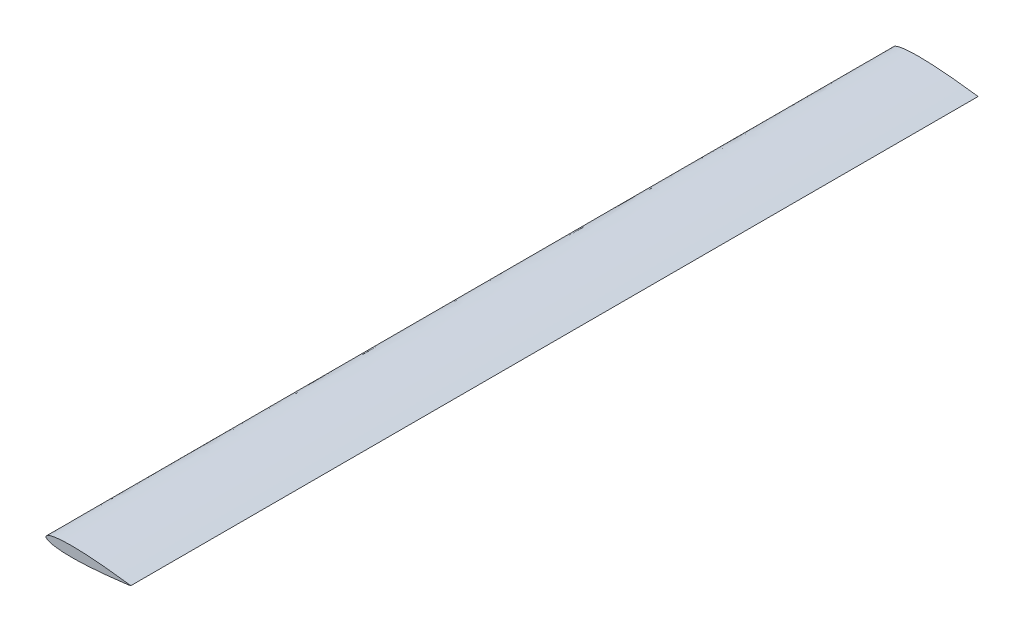
SolidWorks part; units mm, degrees
material "Custom Polymer"
ref_plane "Front Plane" through (0, 0, 0) normal (0, 0, 1) x (1, 0, 0)
ref_plane "Top Plane" through (0, 0, 0) normal (0, 1, 0) x (1, 0, 0)
ref_plane "Right Plane" through (0, 0, 0) normal (1, 0, 0) x (0, 0, -1)
sketch "Sketch1" plane through (0, 0, 0) normal (0, 0, 1) x (1, 0, 0)
  line L0 (0, 0) -> (1000, 0) construction
  spline S4 degree 3 poles (0.4143, 4.3853) (-0.2008, 0.0001) (0.4094, -4.3857) (2.2543, -8.6603) (5.2707, -12.775) (9.422, -16.7475) (14.6946, -20.592) (21.081, -24.312) (28.5717, -27.9033) (37.1535, -31.3578) (46.8093, -34.6651) (57.5186, -37.8143) (69.2578, -40.7934) (82.0003, -43.5917) (95.717, -46.1976) (110.3762, -48.6018) (125.9441, -50.7943) (142.3846, -52.7677) (159.6593, -54.5151) (177.7281, -56.0316) (196.5487, -57.3135) (216.0775, -58.3589) (236.2687, -59.1679) (257.0752, -59.7419) (278.4485, -60.0841) (300.3387, -60.1994) (322.6946, -60.0941) (345.4641, -59.7758) (368.5941, -59.2535) (392.0304, -58.5372) (415.7184, -57.6376) (439.6028, -56.5665) (463.6278, -55.336) (487.7372, -53.9588) (511.8749, -52.4476) (535.9844, -50.8155) (560.0094, -49.0752) (583.8939, -47.2399) (607.5819, -45.322) (631.0183, -43.3341) (654.1483, -41.2882) (676.9179, -39.1961) (699.2738, -37.0696) (721.1639, -34.9196) (742.5371, -32.7573) (763.3433, -30.5932) (783.5341, -28.438) (803.0622, -26.3022) (821.8821, -24.1954) (839.9497, -22.1283) (857.223, -20.1106) (873.6615, -18.1522) (889.2267, -16.2628) (903.8825, -14.4523) (917.5946, -12.7298) (930.3308, -11.1051) (942.0615, -9.5864) (952.7594, -8.1834) (962.3991, -6.9024) (970.9591, -5.7556) (978.4165, -4.737) (984.7625, -3.8911) (989.9579, -3.1155) (994.0559, -2.7031) (996.8878, -1.9572) (999.5116, -2.4521) (1000.4888, 0.7707) (998.6373, 0.7843) (996.9769, 1.1296) (994.0179, 1.481) (989.9767, 2.0732) (984.7604, 2.7864) (978.4232, 3.6639) (970.9642, 4.6823) (962.4063, 5.8413) (952.7678, 7.1321) (942.0716, 8.5471) (930.3425, 10.0787) (917.6081, 11.7175) (903.8979, 13.4551) (889.2441, 15.2818) (873.6809, 17.1884) (857.2446, 19.1649) (839.9736, 21.2016) (821.9083, 23.2886) (803.0908, 25.4162) (783.565, 27.5735) (763.3766, 29.751) (742.5728, 31.9381) (721.202, 34.124) (699.3143, 36.2981) (676.9607, 38.4492) (654.1935, 40.5664) (631.0658, 42.6379) (607.6316, 44.6517) (583.9456, 46.5957) (560.0632, 48.4573) (536.0401, 50.2241) (511.9324, 51.8829) (487.7965, 53.4207) (463.6885, 54.8245) (439.6649, 56.0815) (415.7818, 57.179) (392.0947, 58.1047) (368.6592, 58.8468) (345.5299, 59.3946) (322.7607, 59.7381) (300.4049, 59.868) (278.5146, 59.7768) (257.1409, 59.4583) (236.3338, 58.9072) (216.1417, 58.1205) (196.6118, 57.0967) (177.7898, 55.8354) (159.7194, 54.3389) (142.4427, 52.6106) (126.0001, 50.6553) (110.4297, 48.48) (95.7679, 46.092) (82.0483, 43.5012) (69.3028, 40.717) (57.5603, 37.7508) (46.8475, 34.6134) (37.188, 31.3167) (28.6024, 27.8718) (21.1078, 24.2887) (14.7173, 20.5758) (9.4405, 16.7371) (5.2848, 12.7691) (2.2639, 8.6578) (0.4143, 4.3853) (-0.2008, 0.0001) (0.4094, -4.3857) knots -0.006774 -0.004322 -0.002107 0 0.002107 0.004322 0.006774 0.009559 0.012737 0.016346 0.02041 0.02494 0.02994 0.03541 0.041346 0.047742 0.054587 0.061871 0.06958 0.077699 0.086213 0.095105 0.104356 0.113946 0.123856 0.134064 0.144547 0.155282 0.166246 0.177414 0.188761 0.20026 0.211886 0.223612 0.23541 0.247253 0.259115 0.270966 0.28278 0.294528 0.306184 0.31772 0.329108 0.340322 0.351336 0.362124 0.37266 0.382919 0.392878 0.402513 0.4118 0.42072 0.429249 0.437368 0.445058 0.452301 0.459079 0.465376 0.471177 0.476469 0.481238 0.485474 0.489166 0.492305 0.494884 0.496896 0.498337 0.499202 0.500509 0.500798 0.501663 0.503104 0.505116 0.507695 0.510834 0.514526 0.518762 0.523531 0.528823 0.534624 0.540921 0.547699 0.554942 0.562632 0.570751 0.57928 0.5882 0.597487 0.607122 0.617081 0.62734 0.637876 0.648664 0.659678 0.670892 0.68228 0.693816 0.705472 0.71722 0.729034 0.740885 0.752747 0.76459 0.776388 0.788114 0.79974 0.811239 0.822586 0.833754 0.844718 0.855453 0.865936 0.876144 0.886054 0.895644 0.904895 0.913787 0.922301 0.93042 0.938129 0.945413 0.952258 0.958654 0.96459 0.97006 0.97506 0.97959 0.983654 0.987263 0.990441 0.993226 0.995678 0.997893 1 1.002107 1.004322 1.006774 only from (0, 0) to (0, 0)
  dimension "D1" = 1000
extrude "Boss-Extrude1" add sketch "Sketch1" along normal blind 10000
sketch "Sketch3" plane through (0, 0, 0) normal (0, 0, -1) x (-1, 0, 0)
  line L0 (-46.6725, -5.2388) -> (-46.6725, 5.2387) construction
  line L1 (-27.6225, 5.2388) -> (-27.6225, -5.2388) construction
  line L2 (-7.7788, -3.8184) -> (-7.7788, 3.8184) construction
  line L3 (-71.2788, 3.6758) -> (-71.2788, -3.6758) construction
  line L4 (-46.6725, -5.2388) -> (-46.6725, 5.2387)
  line L5 (-27.6225, 5.2388) -> (-27.6225, -5.2388)
  line L6 (-7.7788, -3.8184) -> (-7.7788, 3.8184)
  line L7 (-71.2788, 3.6758) -> (-71.2788, -3.6758)
  arc A0 (-71.2788, -3.6758) -> (-46.6725, -5.2388) centre (-26.6642, 504.2394) ccw construction
  arc A1 (-46.6725, 5.2387) -> (-71.2788, 3.6758) centre (-26.6642, -504.2394) ccw construction
  circle A2 centre (-35.56, 0) radius 3.1433 construction
  circle A3 centre (-3.0163, 0) radius 2.9766 construction
  arc A4 (-71.2788, -3.6758) -> (-46.6725, -5.2388) centre (-26.6642, 504.2394) ccw
  arc A5 (-46.6725, 5.2387) -> (-71.2788, 3.6758) centre (-26.6642, -504.2394) ccw
  circle A6 centre (-35.56, 0) radius 3.1433
  circle A7 centre (-3.0163, 0) radius 2.9766
  circle A8 centre (-21.2725, 0) radius 3.9688
  circle A9 centre (-53.0225, 0) radius 3.9687
  spline S0 degree 3 poles (8.8377, -0.5571) (8.9155, 0) (8.8377, 0.5571) (8.603, 1.1001) (8.2195, 1.6226) (7.6918, 2.127) (7.0217, 2.615) (6.2101, 3.0872) (5.2582, 3.5429) (4.1677, 3.9812) (2.9408, 4.4007) (1.58, 4.8) (0.0884, 5.1777) (-1.5306, 5.5323) (-3.2734, 5.8624) (-5.1359, 6.1668) (-7.1139, 6.4442) (-9.2026, 6.6938) (-11.3974, 6.9146) (-13.693, 7.106) (-16.0841, 7.2675) (-18.5652, 7.3989) (-21.1304, 7.5003) (-23.7737, 7.5718) (-26.4891, 7.6137) (-29.2701, 7.6269) (-32.1103, 7.6119) (-35.0029, 7.5699) (-37.9414, 7.5019) (-40.9188, 7.4093) (-43.9281, 7.2933) (-46.9624, 7.1556) (-50.0145, 6.9976) (-53.0773, 6.8209) (-56.1437, 6.6272) (-59.2065, 6.4182) (-62.2586, 6.1954) (-65.2928, 5.9606) (-68.3021, 5.7153) (-71.2794, 5.4611) (-74.2178, 5.1995) (-77.1103, 4.9321) (-79.9503, 4.6604) (-82.7312, 4.3857) (-85.4463, 4.1095) (-88.0894, 3.8332) (-90.6544, 3.5579) (-93.1352, 3.2852) (-95.5259, 3.0163) (-97.8211, 2.7524) (-100.0154, 2.4948) (-102.1037, 2.2449) (-104.081, 2.0038) (-105.9428, 1.7727) (-107.6847, 1.5529) (-109.3027, 1.3456) (-110.7928, 1.1519) (-112.1518, 0.9728) (-113.3764, 0.8095) (-114.4637, 0.6629) (-115.4114, 0.534) (-116.2166, 0.423) (-116.8793, 0.3328) (-117.3928, 0.2578) (-117.7687, 0.2134) (-117.9797, 0.1696) (-118.2149, 0.168) (-118.091, -0.2415) (-117.7576, -0.1788) (-117.3979, -0.2737) (-116.8773, -0.3264) (-116.2173, -0.4253) (-115.4111, -0.5332) (-114.4638, -0.6632) (-113.3764, -0.8095) (-112.1518, -0.9729) (-110.7928, -1.1519) (-109.3027, -1.3456) (-107.6847, -1.5529) (-105.9428, -1.7727) (-104.081, -2.0038) (-102.1037, -2.2449) (-100.0154, -2.4948) (-97.8211, -2.7524) (-95.5259, -3.0163) (-93.1352, -3.2852) (-90.6544, -3.5579) (-88.0894, -3.8332) (-85.4463, -4.1095) (-82.7312, -4.3857) (-79.9503, -4.6604) (-77.1103, -4.9321) (-74.2178, -5.1995) (-71.2794, -5.4611) (-68.3021, -5.7153) (-65.2928, -5.9606) (-62.2586, -6.1954) (-59.2065, -6.4182) (-56.1437, -6.6272) (-53.0773, -6.8209) (-50.0145, -6.9976) (-46.9624, -7.1556) (-43.9281, -7.2933) (-40.9188, -7.4093) (-37.9414, -7.5019) (-35.0029, -7.5699) (-32.1103, -7.6119) (-29.2701, -7.6269) (-26.4891, -7.6137) (-23.7737, -7.5718) (-21.1304, -7.5003) (-18.5652, -7.3989) (-16.0841, -7.2675) (-13.693, -7.106) (-11.3974, -6.9146) (-9.2026, -6.6938) (-7.1139, -6.4442) (-5.1359, -6.1668) (-3.2734, -5.8624) (-1.5306, -5.5323) (0.0884, -5.1777) (1.58, -4.8) (2.9408, -4.4007) (4.1677, -3.9812) (5.2582, -3.5429) (6.2101, -3.0872) (7.0217, -2.615) (7.6918, -2.127) (8.2195, -1.6226) (8.603, -1.1001) (8.8377, -0.5571) (8.9155, 0) (8.8377, 0.5571) knots -0.006774 -0.004322 -0.002107 0 0.002107 0.004322 0.006774 0.009559 0.012737 0.016346 0.02041 0.02494 0.02994 0.03541 0.041346 0.047742 0.054587 0.061871 0.06958 0.077699 0.086213 0.095105 0.104356 0.113946 0.123856 0.134064 0.144547 0.155282 0.166246 0.177414 0.188761 0.20026 0.211886 0.223612 0.23541 0.247253 0.259115 0.270966 0.28278 0.294528 0.306184 0.31772 0.329108 0.340322 0.351336 0.362124 0.37266 0.382919 0.392878 0.402513 0.4118 0.42072 0.429249 0.437368 0.445058 0.452301 0.459079 0.465376 0.471177 0.476469 0.481238 0.485474 0.489166 0.492305 0.494884 0.496896 0.498337 0.499202 0.499491 0.500798 0.501663 0.503104 0.505116 0.507695 0.510834 0.514526 0.518762 0.523531 0.528823 0.534624 0.540921 0.547699 0.554942 0.562632 0.570751 0.57928 0.5882 0.597487 0.607122 0.617081 0.62734 0.637876 0.648664 0.659678 0.670892 0.68228 0.693816 0.705472 0.71722 0.729034 0.740885 0.752747 0.76459 0.776388 0.788114 0.79974 0.811239 0.822586 0.833754 0.844718 0.855453 0.865936 0.876144 0.886054 0.895644 0.904895 0.913787 0.922301 0.93042 0.938129 0.945413 0.952258 0.958654 0.96459 0.97006 0.97506 0.97959 0.983654 0.987263 0.990441 0.993226 0.995678 0.997893 1 1.002107 1.004322 1.006774 only from (8.89, 0) to (8.89, 0) construction
  spline S1 degree 3 poles (-27.6225, 5.2388) (-20.0778, 5.0313) (-13.2778, 4.5445) (-7.7788, 3.8184) knots 0 0 0 0 1 1 1 1 weights 1 0.972728 0.972728 1 construction
  spline S2 degree 3 poles (-27.6225, -5.2388) (-20.0778, -5.0313) (-13.2778, -4.5445) (-7.7788, -3.8184) knots 0 0 0 0 1 1 1 1 weights 1 0.972728 0.972728 1 construction
  spline S3 degree 3 poles (8.8377, -0.5571) (8.9155, 0) (8.8377, 0.5571) (8.603, 1.1001) (8.2195, 1.6226) (7.6918, 2.127) (7.0217, 2.615) (6.2101, 3.0872) (5.2582, 3.5429) (4.1677, 3.9812) (2.9408, 4.4007) (1.58, 4.8) (0.0884, 5.1777) (-1.5306, 5.5323) (-3.2734, 5.8624) (-5.1359, 6.1668) (-7.1139, 6.4442) (-9.2026, 6.6938) (-11.3974, 6.9146) (-13.693, 7.106) (-16.0841, 7.2675) (-18.5652, 7.3989) (-21.1304, 7.5003) (-23.7737, 7.5718) (-26.4891, 7.6137) (-29.2701, 7.6269) (-32.1103, 7.6119) (-35.0029, 7.5699) (-37.9414, 7.5019) (-40.9188, 7.4093) (-43.9281, 7.2933) (-46.9624, 7.1556) (-50.0145, 6.9976) (-53.0773, 6.8209) (-56.1437, 6.6272) (-59.2065, 6.4182) (-62.2586, 6.1954) (-65.2928, 5.9606) (-68.3021, 5.7153) (-71.2794, 5.4611) (-74.2178, 5.1995) (-77.1103, 4.9321) (-79.9503, 4.6604) (-82.7312, 4.3857) (-85.4463, 4.1095) (-88.0894, 3.8332) (-90.6544, 3.5579) (-93.1352, 3.2852) (-95.5259, 3.0163) (-97.8211, 2.7524) (-100.0154, 2.4948) (-102.1037, 2.2449) (-104.081, 2.0038) (-105.9428, 1.7727) (-107.6847, 1.5529) (-109.3027, 1.3456) (-110.7928, 1.1519) (-112.1518, 0.9728) (-113.3764, 0.8095) (-114.4637, 0.6629) (-115.4114, 0.534) (-116.2166, 0.423) (-116.8793, 0.3328) (-117.3928, 0.2578) (-117.7687, 0.2134) (-117.9797, 0.1696) (-118.2149, 0.168) (-118.091, -0.2415) (-117.7576, -0.1788) (-117.3979, -0.2737) (-116.8773, -0.3264) (-116.2173, -0.4253) (-115.4111, -0.5332) (-114.4638, -0.6632) (-113.3764, -0.8095) (-112.1518, -0.9729) (-110.7928, -1.1519) (-109.3027, -1.3456) (-107.6847, -1.5529) (-105.9428, -1.7727) (-104.081, -2.0038) (-102.1037, -2.2449) (-100.0154, -2.4948) (-97.8211, -2.7524) (-95.5259, -3.0163) (-93.1352, -3.2852) (-90.6544, -3.5579) (-88.0894, -3.8332) (-85.4463, -4.1095) (-82.7312, -4.3857) (-79.9503, -4.6604) (-77.1103, -4.9321) (-74.2178, -5.1995) (-71.2794, -5.4611) (-68.3021, -5.7153) (-65.2928, -5.9606) (-62.2586, -6.1954) (-59.2065, -6.4182) (-56.1437, -6.6272) (-53.0773, -6.8209) (-50.0145, -6.9976) (-46.9624, -7.1556) (-43.9281, -7.2933) (-40.9188, -7.4093) (-37.9414, -7.5019) (-35.0029, -7.5699) (-32.1103, -7.6119) (-29.2701, -7.6269) (-26.4891, -7.6137) (-23.7737, -7.5718) (-21.1304, -7.5003) (-18.5652, -7.3989) (-16.0841, -7.2675) (-13.693, -7.106) (-11.3974, -6.9146) (-9.2026, -6.6938) (-7.1139, -6.4442) (-5.1359, -6.1668) (-3.2734, -5.8624) (-1.5306, -5.5323) (0.0884, -5.1777) (1.58, -4.8) (2.9408, -4.4007) (4.1677, -3.9812) (5.2582, -3.5429) (6.2101, -3.0872) (7.0217, -2.615) (7.6918, -2.127) (8.2195, -1.6226) (8.603, -1.1001) (8.8377, -0.5571) (8.9155, 0) (8.8377, 0.5571) knots -0.006774 -0.004322 -0.002107 0 0.002107 0.004322 0.006774 0.009559 0.012737 0.016346 0.02041 0.02494 0.02994 0.03541 0.041346 0.047742 0.054587 0.061871 0.06958 0.077699 0.086213 0.095105 0.104356 0.113946 0.123856 0.134064 0.144547 0.155282 0.166246 0.177414 0.188761 0.20026 0.211886 0.223612 0.23541 0.247253 0.259115 0.270966 0.28278 0.294528 0.306184 0.31772 0.329108 0.340322 0.351336 0.362124 0.37266 0.382919 0.392878 0.402513 0.4118 0.42072 0.429249 0.437368 0.445058 0.452301 0.459079 0.465376 0.471177 0.476469 0.481238 0.485474 0.489166 0.492305 0.494884 0.496896 0.498337 0.499202 0.499491 0.500798 0.501663 0.503104 0.505116 0.507695 0.510834 0.514526 0.518762 0.523531 0.528823 0.534624 0.540921 0.547699 0.554942 0.562632 0.570751 0.57928 0.5882 0.597487 0.607122 0.617081 0.62734 0.637876 0.648664 0.659678 0.670892 0.68228 0.693816 0.705472 0.71722 0.729034 0.740885 0.752747 0.76459 0.776388 0.788114 0.79974 0.811239 0.822586 0.833754 0.844718 0.855453 0.865936 0.876144 0.886054 0.895644 0.904895 0.913787 0.922301 0.93042 0.938129 0.945413 0.952258 0.958654 0.96459 0.97006 0.97506 0.97959 0.983654 0.987263 0.990441 0.993226 0.995678 0.997893 1 1.002107 1.004322 1.006774 only from (8.89, 0) to (8.89, 0)
  spline S4 degree 3 poles (-27.6225, 5.2388) (-20.0778, 5.0313) (-13.2778, 4.5445) (-7.7788, 3.8184) knots 0 0 0 0 1 1 1 1 weights 1 0.972728 0.972728 1
  spline S5 degree 3 poles (-27.6225, -5.2388) (-20.0778, -5.0313) (-13.2778, -4.5445) (-7.7788, -3.8184) knots 0 0 0 0 1 1 1 1 weights 1 0.972728 0.972728 1
  dimension "D2" = 7.9375
  dimension "D3" = 7.9375
  dimension "D1" = 6.35
  dimension "D4" = 6.35
extrude "Boss-Extrude2" [suppressed] add sketch "Sketch3" along normal blind 6.35
pattern_linear "LPattern1" [suppressed] count 3 spacing 69.85 of bodies 102
sketch "Sketch5" [suppressed] plane through (0, 0, -139.7) normal (0, 0, 1) x (1, 0, 0)
  line L2 (71.2787, -3.6758) -> (71.2788, 3.6758)
  line L3 (46.6725, 5.2387) -> (46.6725, -5.2388)
  line L4 (71.2787, -3.6758) -> (71.2788, 3.6758)
  line L5 (46.6725, 5.2387) -> (46.6725, -5.2388)
  arc A2 (46.6725, -5.2388) -> (71.2787, -3.6758) centre (26.6642, 504.2394) ccw
  arc A3 (71.2788, 3.6758) -> (46.6725, 5.2387) centre (26.6642, -504.2394) ccw
  arc A4 (46.6725, -5.2388) -> (71.2787, -3.6758) centre (26.6642, 504.2394) ccw
  arc A5 (71.2788, 3.6758) -> (46.6725, 5.2387) centre (26.6642, -504.2394) ccw
  dimension "D1" = 0
extrude "Cut-Extrude1" [suppressed] cut sketch "Sketch5" against normal blind 6.35
sketch "Sketch6" [suppressed] plane through (0, 0, -139.7) normal (0, 0, 1) x (1, 0, 0)
  line L2 (27.6225, -5.2388) -> (27.6225, 5.2388)
  line L3 (7.7788, 3.8184) -> (7.7788, -3.8184)
  line L4 (27.6225, -5.2388) -> (27.6225, 5.2388)
  line L5 (7.7788, 3.8184) -> (7.7788, -3.8184)
  spline S2 degree 3 poles (7.7788, -3.8184) (13.2778, -4.5445) (20.0778, -5.0313) (27.6225, -5.2388) knots 0 0 0 0 1 1 1 1 weights 1 0.972728 0.972728 1
  spline S3 degree 3 poles (27.6225, 5.2388) (20.0778, 5.0313) (13.2778, 4.5445) (7.7788, 3.8184) knots 0 0 0 0 1 1 1 1 weights 1 0.972728 0.972728 1
  spline S4 degree 3 poles (7.7788, -3.8184) (13.2778, -4.5445) (20.0778, -5.0313) (27.6225, -5.2388) knots 0 0 0 0 1 1 1 1 weights 1 0.972728 0.972728 1
  spline S5 degree 3 poles (27.6225, 5.2388) (20.0778, 5.0313) (13.2778, 4.5445) (7.7788, 3.8184) knots 0 0 0 0 1 1 1 1 weights 1 0.972728 0.972728 1
  dimension "D1" = 0
extrude "Cut-Extrude2" [suppressed] cut sketch "Sketch6" against normal blind 6.35
sketch "Sketch8" [suppressed] plane through (0, 0, 609.6) normal (0, 0, 1) x (1, 0, 0)
  line L0 (35.56, 0) -> (-8.89, 0) construction
  spline S0 degree 3 poles (-8.8377, 0.5571) (-8.9155, 0) (-8.8377, -0.5571) (-8.603, -1.1001) (-8.2195, -1.6226) (-7.6918, -2.127) (-7.0217, -2.615) (-6.2101, -3.0872) (-5.2582, -3.5429) (-4.1677, -3.9812) (-2.9408, -4.4007) (-1.58, -4.8) (-0.0884, -5.1777) (1.5306, -5.5323) (3.2734, -5.8624) (5.1359, -6.1668) (7.1139, -6.4442) (9.2026, -6.6938) (11.3974, -6.9146) (13.693, -7.106) (16.0841, -7.2675) (18.5652, -7.3989) (21.1304, -7.5003) (23.7737, -7.5718) (26.4891, -7.6137) (29.2701, -7.6269) (32.1103, -7.6119) (35.0029, -7.5699) (37.9414, -7.5019) (40.9188, -7.4093) (43.9281, -7.2933) (46.9624, -7.1556) (50.0145, -6.9976) (53.0773, -6.8209) (56.1437, -6.6272) (59.2065, -6.4182) (62.2586, -6.1954) (65.2928, -5.9606) (68.3021, -5.7153) (71.2794, -5.4611) (74.2178, -5.1995) (77.1103, -4.9321) (79.9503, -4.6604) (82.7312, -4.3857) (85.4463, -4.1095) (88.0894, -3.8332) (90.6544, -3.5579) (93.1352, -3.2852) (95.5259, -3.0163) (97.8211, -2.7524) (100.0154, -2.4948) (102.1037, -2.2449) (104.081, -2.0038) (105.9428, -1.7727) (107.6847, -1.5529) (109.3027, -1.3456) (110.7928, -1.1519) (112.1518, -0.9729) (113.3764, -0.8095) (114.4638, -0.6632) (115.4111, -0.5332) (116.2173, -0.4253) (116.8773, -0.3264) (117.3979, -0.2737) (117.7576, -0.1788) (118.091, -0.2415) (118.2149, 0.168) (117.9797, 0.1696) (117.7687, 0.2134) (117.3928, 0.2578) (116.8793, 0.3328) (116.2166, 0.423) (115.4114, 0.534) (114.4637, 0.6629) (113.3764, 0.8095) (112.1518, 0.9728) (110.7928, 1.1519) (109.3027, 1.3456) (107.6847, 1.5529) (105.9428, 1.7727) (104.081, 2.0038) (102.1037, 2.2449) (100.0154, 2.4948) (97.8211, 2.7524) (95.5259, 3.0163) (93.1352, 3.2852) (90.6544, 3.5579) (88.0894, 3.8332) (85.4463, 4.1095) (82.7312, 4.3857) (79.9503, 4.6604) (77.1103, 4.9321) (74.2178, 5.1995) (71.2794, 5.4611) (68.3021, 5.7153) (65.2928, 5.9606) (62.2586, 6.1954) (59.2065, 6.4182) (56.1437, 6.6272) (53.0773, 6.8209) (50.0145, 6.9976) (46.9624, 7.1556) (43.9281, 7.2933) (40.9188, 7.4093) (37.9414, 7.5019) (35.0029, 7.5699) (32.1103, 7.6119) (29.2701, 7.6269) (26.4891, 7.6137) (23.7737, 7.5718) (21.1304, 7.5003) (18.5652, 7.3989) (16.0841, 7.2675) (13.693, 7.106) (11.3974, 6.9146) (9.2026, 6.6938) (7.1139, 6.4442) (5.1359, 6.1668) (3.2734, 5.8624) (1.5306, 5.5323) (-0.0884, 5.1777) (-1.58, 4.8) (-2.9408, 4.4007) (-4.1677, 3.9812) (-5.2582, 3.5429) (-6.2101, 3.0872) (-7.0217, 2.615) (-7.6918, 2.127) (-8.2195, 1.6226) (-8.603, 1.1001) (-8.8377, 0.5571) (-8.9155, 0) (-8.8377, -0.5571) knots -0.006774 -0.004322 -0.002107 0 0.002107 0.004322 0.006774 0.009559 0.012737 0.016346 0.02041 0.02494 0.02994 0.03541 0.041346 0.047742 0.054587 0.061871 0.06958 0.077699 0.086213 0.095105 0.104356 0.113946 0.123856 0.134064 0.144547 0.155282 0.166246 0.177414 0.188761 0.20026 0.211886 0.223612 0.23541 0.247253 0.259115 0.270966 0.28278 0.294528 0.306184 0.31772 0.329108 0.340322 0.351336 0.362124 0.37266 0.382919 0.392878 0.402513 0.4118 0.42072 0.429249 0.437368 0.445058 0.452301 0.459079 0.465376 0.471177 0.476469 0.481238 0.485474 0.489166 0.492305 0.494884 0.496896 0.498337 0.499202 0.500509 0.500798 0.501663 0.503104 0.505116 0.507695 0.510834 0.514526 0.518762 0.523531 0.528823 0.534624 0.540921 0.547699 0.554942 0.562632 0.570751 0.57928 0.5882 0.597487 0.607122 0.617081 0.62734 0.637876 0.648664 0.659678 0.670892 0.68228 0.693816 0.705472 0.71722 0.729034 0.740885 0.752747 0.76459 0.776388 0.788114 0.79974 0.811239 0.822586 0.833754 0.844718 0.855453 0.865936 0.876144 0.886054 0.895644 0.904895 0.913787 0.922301 0.93042 0.938129 0.945413 0.952258 0.958654 0.96459 0.97006 0.97506 0.97959 0.983654 0.987263 0.990441 0.993226 0.995678 0.997893 1 1.002107 1.004322 1.006774 only from (-8.89, 0) to (-8.89, 0) construction
